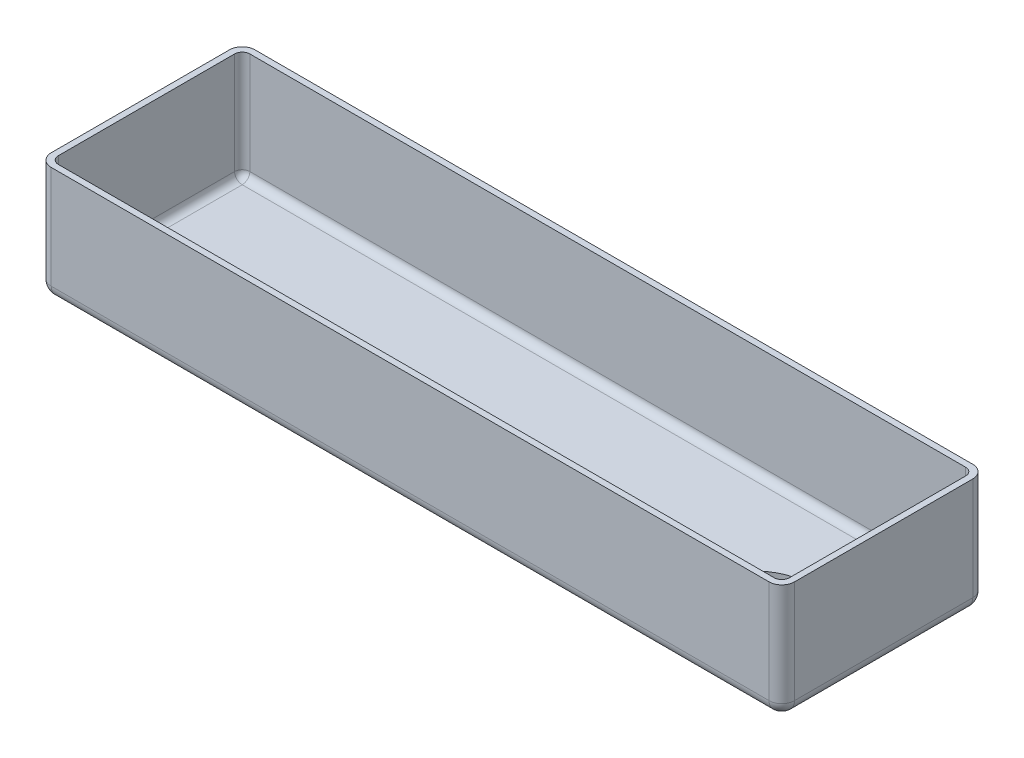
SolidWorks part; units mm, degrees
material "NEOPRENE"
ref_plane "Front" through (0, 0, 0) normal (0, 0, 1) x (1, 0, 0)
ref_plane "Top" through (0, 0, 0) normal (0, 1, 0) x (1, 0, 0)
ref_plane "Right" through (0, 0, 0) normal (1, 0, 0) x (0, 0, -1)
sketch "Sketch1" plane through (0, 0, 0) normal (0, 1, 0) x (1, 0, 0)
  line L0 (-91.1606, 0) -> (-92.6846, 0) construction
  line L1 (-92.6846, 25.4) -> (92.6846, 25.4)
  line L2 (-92.6846, 25.4) -> (-92.6846, -25.4)
  line L3 (-92.6846, -25.4) -> (92.6846, -25.4)
  line L4 (92.6846, 25.4) -> (92.6846, -25.4)
  line L5 (-92.6846, 25.4) -> (92.6846, -25.4) construction
  line L6 (-92.6846, -25.4) -> (92.6846, 25.4) construction
  line L7 (91.1606, 23.876) -> (-91.1606, 23.876)
  line L8 (91.1606, 23.876) -> (91.1606, -23.876)
  line L9 (91.1606, -23.876) -> (-91.1606, -23.876)
  line L10 (-91.1606, 23.876) -> (-91.1606, -23.876)
  line L11 (91.1606, 23.876) -> (-91.1606, -23.876) construction
  line L12 (91.1606, -23.876) -> (-91.1606, 23.876) construction
  line L13 (0, 23.876) -> (0, 25.4) construction
  point P0 (0, 0)
  point P6 (0, 0)
  dimension "D1" = 182.3212
  dimension "D2" = 50.8
  dimension "THICKNESS" = 1.524
extrude "Boss-Extrude1" add sketch "Sketch1" along normal blind 27.305
sketch "Sketch2" plane through (0, 0, 0) normal (0, -1, 0) x (1, 0, 0)
  line L4 (92.6846, -25.4) -> (92.6846, 25.4)
  line L5 (92.6846, 25.4) -> (-92.6846, 25.4)
  line L6 (-92.6846, 25.4) -> (-92.6846, -25.4)
  line L7 (-92.6846, -25.4) -> (92.6846, -25.4)
  line L8 (92.6846, -25.4) -> (92.6846, 25.4)
  line L9 (92.6846, 25.4) -> (-92.6846, 25.4)
  line L10 (-92.6846, 25.4) -> (-92.6846, -25.4)
  line L11 (-92.6846, -25.4) -> (92.6846, -25.4)
  dimension "D1" = 0
extrude "Boss-Extrude2" add sketch "Sketch2" along normal blind 1.524
fillet "Fillet1" radius 1.905 8 edges at (91.1606, 13.6525, -23.876) (91.1606, 13.6525, 23.876) (-91.1606, 13.6525, 23.876) (-91.1606, 13.6525, -23.876) (91.1606, 0, 0) (0, 0, 23.876) (-91.1606, 0, 0) (0, 0, -23.876)
fillet "Fillet2" radius 3.175 8 edges at (-92.6846, -1.524, 0) (0, -1.524, 25.4) (92.6846, -1.524, 0) (0, -1.524, -25.4) (-92.6846, 12.8905, -25.4) (92.6846, 12.8905, -25.4) (92.6846, 12.8905, 25.4) (-92.6846, 12.8905, 25.4)
sketch "Sketch3" plane through (0, -1.524, 0) normal (0, -1, 0) x (1, 0, 0)
  circle A0 centre (45, -2.3792) radius 4.826
  circle A1 centre (-45.2, -2.3792) radius 4.826
  point P4 (-45.2, -2.3792)
  point P6 (45, -2.3792)
  dimension "D1" = 9.652
extrude "Cut-Extrude1" [suppressed] cut sketch "Sketch3" against normal through all and the other way blind 2.54
sketch "Sketch4" plane through (0, -1.524, 0) normal (0, -1, 0) x (1, 0, 0)
  line L0 (-89.5096, 25.4) -> (89.5096, 25.4) construction
  line L1 (92.6846, 22.225) -> (92.6846, -22.225) construction
  circle A0 centre (67.2846, 6.35) radius 12.7
  point P4 (0, 0)
  dimension "D1" = 25.4
  dimension "D2" = 19.05
  dimension "D3" = 25.4
extrude "Cut-Extrude2" cut sketch "Sketch4" against normal through all
equation "\"D1@Boss-Extrude2\"=\"THICKNESS\""
